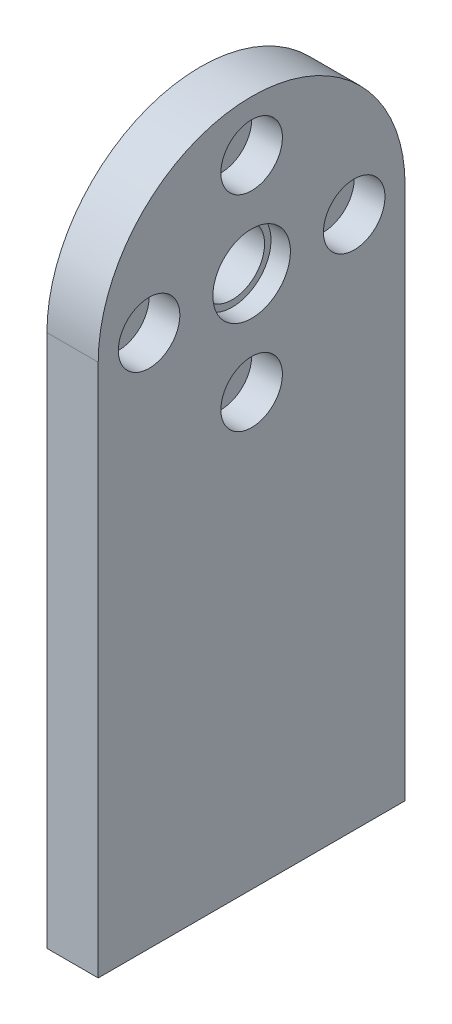
SolidWorks part; units mm, degrees
ref_plane "Front Plane" through (0, 0, 0) normal (0, 0, 1) x (1, 0, 0)
ref_plane "Top Plane" through (0, 0, 0) normal (0, 1, 0) x (1, 0, 0)
ref_plane "Right Plane" through (0, 0, 0) normal (1, 0, 0) x (0, 0, -1)
sketch "Sketch1" plane through (-13.275, 0, 0) normal (1, 0, 0) x (0, 0, -1)
  line L0 (-47.5, -165.1) -> (-47.5, 0)
  line L1 (47.5, 0) -> (47.5, -165.1)
  line L2 (47.5, -165.1) -> (-47.5, -165.1)
  arc A0 (-47.5, 0) -> (47.5, 0) centre (0, 0) cw
  circle A1 centre (0, 0) radius 60 construction
  circle A2 centre (0, 0) radius 47.5 construction
  dimension "D1" = 165.1
extrude "Boss-Extrude1" add sketch "Sketch1" against normal up to surface (15.875 mm away)
sketch "Sketch2" plane through (-13.275, 0, 0) normal (1, 0, 0) x (0, 0, -1)
  circle A0 centre (0, 0) radius 12
  dimension "D1" = 24
extrude "Cut-Extrude1" cut sketch "Sketch2" against normal blind 6
sketch "Sketch3" plane through (-19.275, 0, 0) normal (1, 0, 0) x (0, 0, -1)
  circle A0 centre (0, 0) radius 10
  dimension "D1" = 20
extrude "Cut-Extrude2" cut sketch "Sketch3" against normal through all
sketch "Sketch4" plane through (-29.15, 0, 0) normal (-1, 0, 0) x (0, 0, 1)
  circle A0 centre (0, -31.75) radius 3.2639
  circle A1 centre (31.75, 0) radius 3.2639
  circle A2 centre (-31.75, 0) radius 3.2639
  circle A3 centre (0, 31.75) radius 3.2639
  dimension "D1" = 6.5278
extrude "Cut-Extrude3" cut sketch "Sketch4" against normal through all
sketch "Sketch5" plane through (-13.275, 0, 0) normal (1, 0, 0) x (0, 0, -1)
  circle A0 centre (-31.75, 0) radius 9.525
  circle A1 centre (0, 31.75) radius 9.525
  circle A2 centre (31.75, 0) radius 9.525
  circle A3 centre (0, -31.75) radius 9.525
  dimension "D1" = 19.05
extrude "Cut-Extrude4" cut sketch "Sketch5" against normal offset from surface (9.525 mm away) 6.35 up to face at (-29.15, -31.75, 3.2639)
